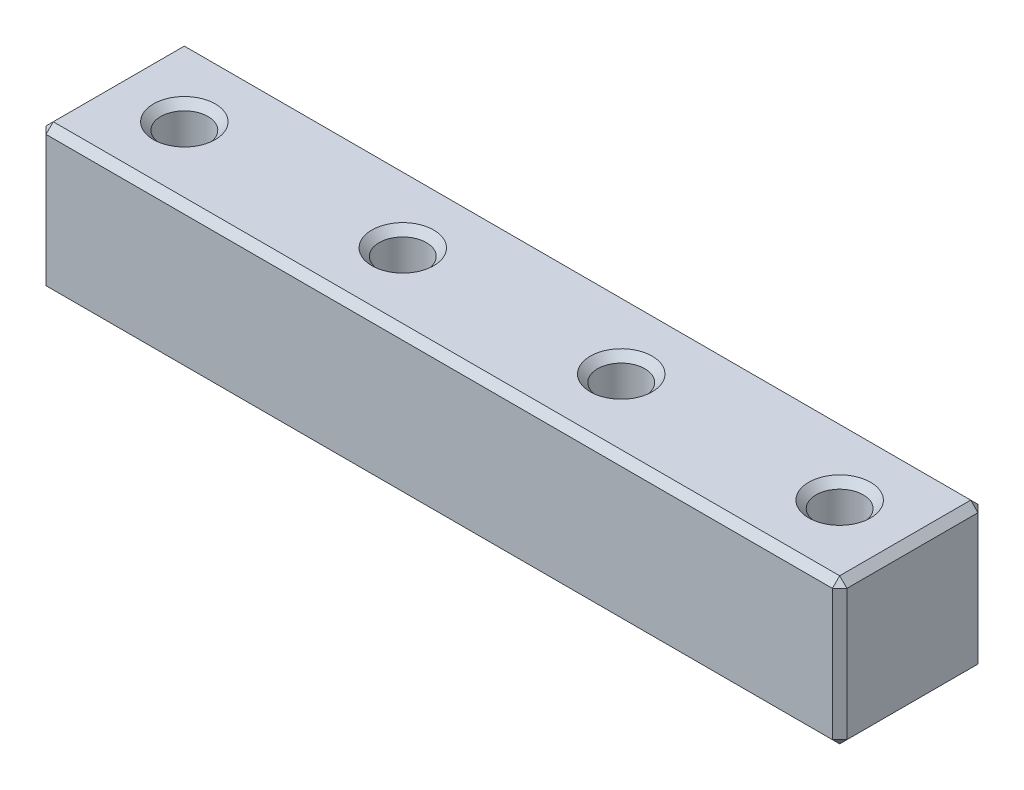
SolidWorks part; units mm, degrees
material "HDPE, Black"
ref_plane "Front Plane" through (0, 0, 0) normal (0, 0, 1) x (1, 0, 0)
ref_plane "Top Plane" through (0, 0, 0) normal (0, 1, 0) x (1, 0, 0)
ref_plane "Right Plane" through (0, 0, 0) normal (1, 0, 0) x (0, 0, -1)
sketch "Sketch1" plane through (0, 0, 0) normal (0, 1, 0) x (1, 0, 0)
  line L0 (-45, 0) -> (-15, 0) construction
  line L1 (-55, -10) -> (55, -10)
  line L2 (-55, -10) -> (-55, 10)
  line L3 (-55, 10) -> (55, 10)
  line L4 (55, -10) -> (55, 10)
  line L5 (-55, -10) -> (55, 10) construction
  line L6 (-55, 10) -> (55, -10) construction
  line L7 (-15, 0) -> (15, 0) construction
  line L9 (15, 0) -> (45, 0) construction
  circle A0 centre (-45, 0) radius 3.25
  circle A1 centre (-15, 0) radius 3.25
  circle A3 centre (15, 0) radius 3.25
  circle A4 centre (45, 0) radius 3.25
  point P0 (0, 0)
  point P10 (0, 0)
  point P11 (0.4853, -2.0451)
  point P16 (0, 0)
  point P17 (0, 0)
  dimension "D4" = 6.5
  dimension "D1" = 20
  dimension "D2" = 110
  dimension "D3" = 30
extrude "Boss-Extrude1" add sketch "Sketch1" along normal blind 20
chamfer "Chamfer1" distance 1 angle 45 20 edges at (55, 20, 0) (55, 0, 0) (55, 10, -10) (0, 20, -10) (0, 0, -10) (-55, 10, -10) (-55, 20, 0) (-55, 0, 0) (-55, 10, 10) (0, 20, 10) (55, 10, 10) (0, 0, 10) (45, 0, 3.25) (45, 20, 3.25) (15, 0, 3.25) (15, 20, 3.25) (-15, 0, 3.25) (-15, 20, 3.25) (-45, 0, 3.25) (-45, 20, 3.25)
